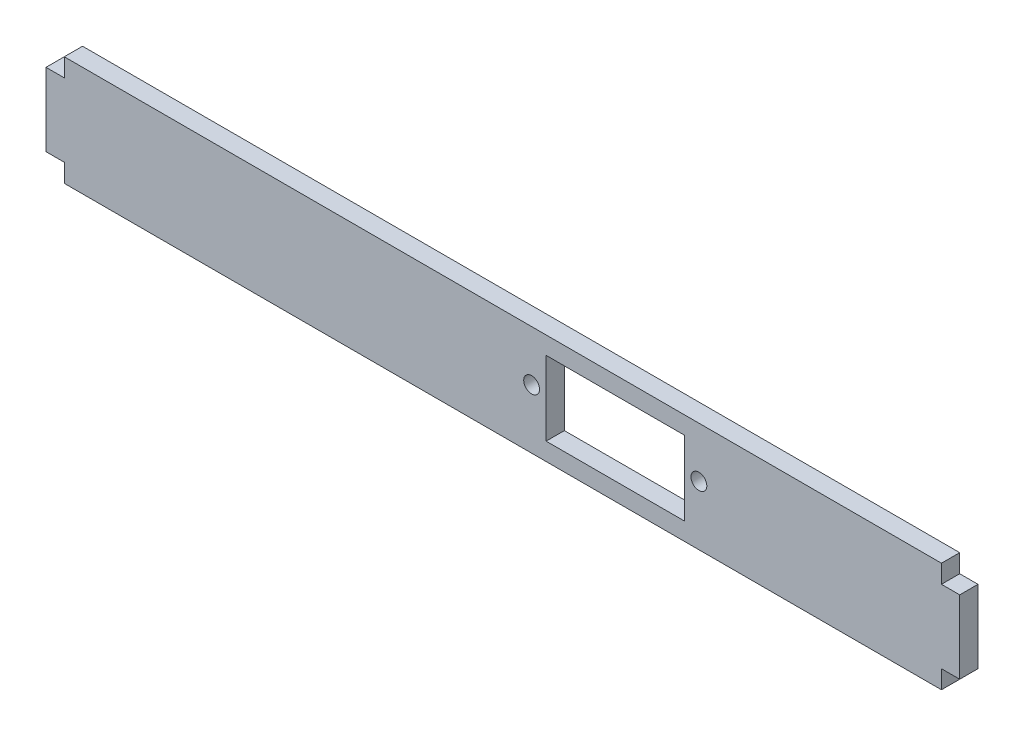
SolidWorks part; units mm, degrees
ref_plane "Front Plane" through (0, 0, 0) normal (0, 0, 1) x (1, 0, 0)
ref_plane "Top Plane" through (0, 0, 0) normal (0, 1, 0) x (1, 0, 0)
ref_plane "Right Plane" through (0, 0, 0) normal (1, 0, 0) x (0, 0, -1)
sketch "Sketch1" plane through (0, 0, 0) normal (0, 0, 1) x (1, 0, 0)
  line L1 (-75, 9) -> (75, 9)
  line L2 (-75, 9) -> (-75, -9)
  line L3 (-75, -9) -> (75, -9)
  line L4 (75, 9) -> (75, -9)
  line L5 (-75, 9) -> (75, -9) construction
  line L6 (-75, -9) -> (75, 9) construction
  point P0 (0, 0)
  dimension "D1" = 150
  dimension "D2" = 18
extrude "Boss-Extrude1" add sketch "Sketch1" along normal blind 3
sketch "Sketch2" plane through (0, 0, 0) normal (0, 0, -1) x (-1, 0, 0)
  line L0 (-75, -9) -> (-75, 9) construction
  line L1 (-29.8, 6.1) -> (-7.1, 6.1)
  line L2 (-29.8, 6.1) -> (-29.8, -6.1)
  line L3 (-29.8, -6.1) -> (-7.1, -6.1)
  line L4 (-7.1, 6.1) -> (-7.1, -6.1)
  line L6 (-75, 0) -> (75, 0) construction
  line L7 (75, 9) -> (75, -9) construction
  dimension "D1" = 22.7
  dimension "D2" = 12.2
  dimension "D3" = 45.2
extrude "Cut-Extrude1" cut sketch "Sketch2" against normal blind 3
sketch "Sketch3" plane through (0, 0, 3) normal (0, 0, 1) x (1, 0, 0)
  circle A0 centre (32.175, 0.1) radius 1.2
extrude "Boss-Extrude2" add sketch "Sketch3" against normal blind 3
sketch "Sketch4" plane through (0, 0, 0) normal (0, 0, -1) x (-1, 0, 0)
  line L3 (-18.45, 6.1) -> (-18.45, -6.1) construction
  line L4 (-7.1, 6.1) -> (-29.8, 6.1) construction
  line L5 (-29.8, -6.1) -> (-7.1, -6.1) construction
  line L6 (-29.8, 6.1) -> (-29.8, -6.1) construction
  circle A0 centre (-32.18, 0.7232) radius 1.3
  circle A1 centre (-4.72, 0.7232) radius 1.3
  dimension "D1" = 2.6
  dimension "D2" = 2.38
extrude "Cut-Extrude2" cut sketch "Sketch4" against normal blind 3
sketch "Sketch5" plane through (0, 0, 0) normal (0, 0, -1) x (-1, 0, 0)
  line L1 (-75, 9) -> (-72, 9)
  line L2 (-75, 9) -> (-75, 6)
  line L3 (-75, 6) -> (-72, 6)
  line L4 (-72, 9) -> (-72, 6)
  dimension "D1" = 3
  dimension "D2" = 3
extrude "Cut-Extrude3" cut sketch "Sketch5" against normal blind 3
mirror "Mirror1" about plane through (0, 0, 0) normal (0, 1, 0) of "Cut-Extrude3"
mirror "Mirror2" about plane through (0, 0, 0) normal (1, 0, 0) of "Mirror1"
